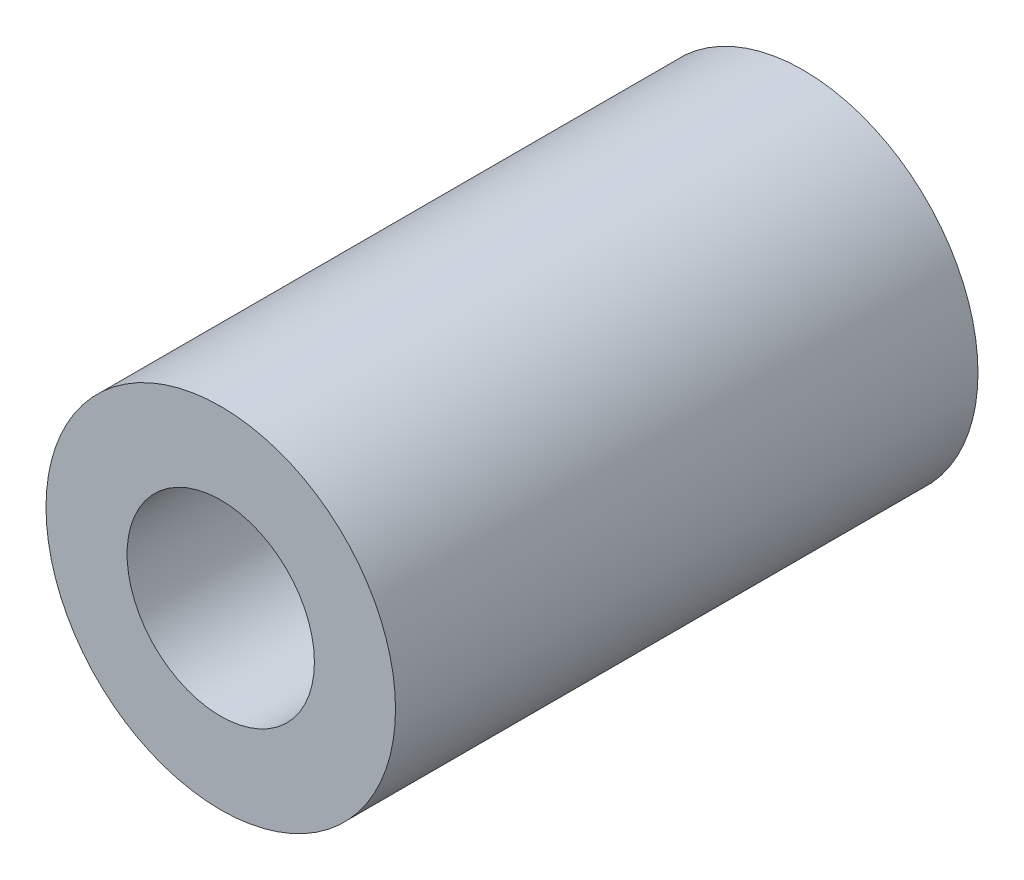
SolidWorks part; units mm, degrees
material "6061-T6 (SS)"
ref_plane "Front Plane" through (0, 0, 0) normal (0, 0, 1) x (1, 0, 0)
ref_plane "Top Plane" through (0, 0, 0) normal (0, 1, 0) x (1, 0, 0)
ref_plane "Right Plane" through (0, 0, 0) normal (1, 0, 0) x (0, 0, -1)
sketch "Sketch1" plane through (0, 0, 0) normal (0, 0, 1) x (1, 0, 0)
  circle A0 centre (0, 0) radius 4.7625
  circle A1 centre (0, 0) radius 2.5527
  dimension "D1" = 5.1054
  dimension "D2" = 9.525
extrude "Boss-Extrude1" add sketch "Sketch1" along normal mid plane 15.875 contours A0 A1 region at (-4.6278, 0, 0)
